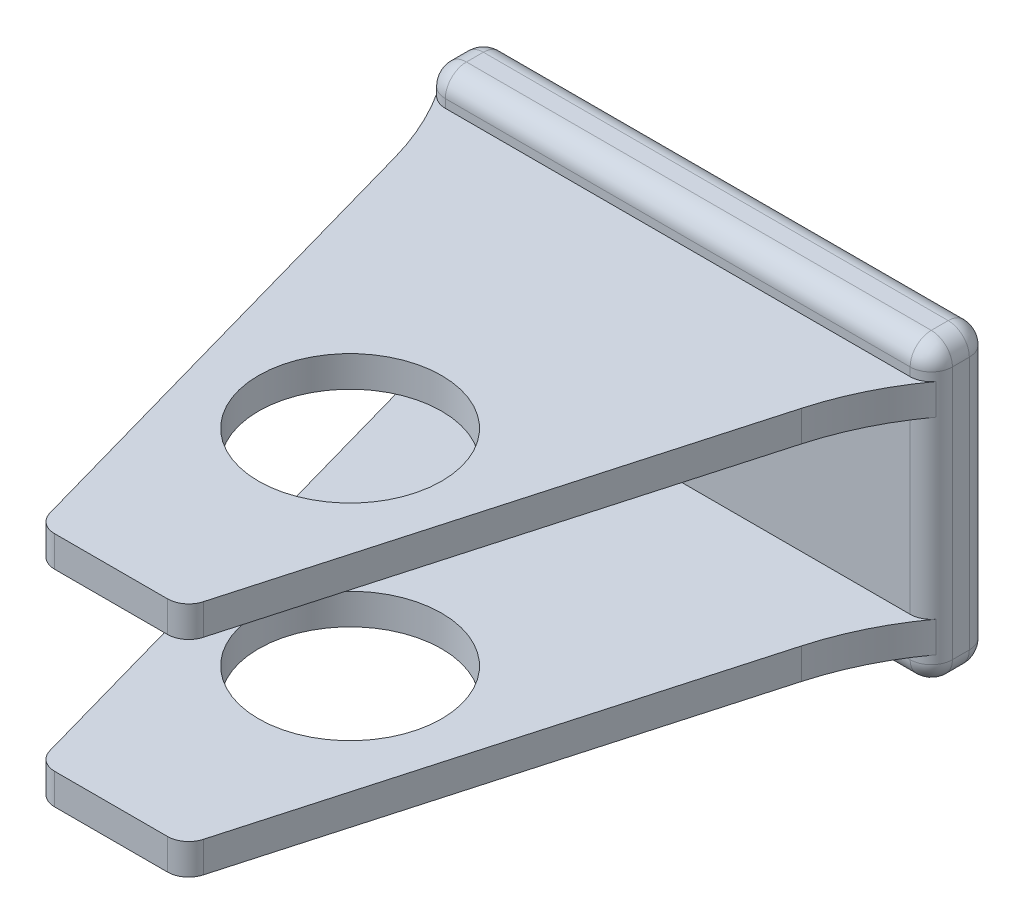
SolidWorks part; units mm, degrees
ref_plane "Front Plane" through (0, 0, 0) normal (0, 0, 1) x (1, 0, 0)
ref_plane "Top Plane" through (0, 0, 0) normal (0, 1, 0) x (1, 0, 0)
ref_plane "Right Plane" through (0, 0, 0) normal (1, 0, 0) x (0, 0, -1)
sketch "Sketch1" plane through (0, 0, 0) normal (0, 0, 1) x (1, 0, 0)
  line L1 (-60, -35) -> (60, -35)
  line L2 (-60, -35) -> (-60, 35)
  line L3 (-60, 35) -> (60, 35)
  line L4 (60, -35) -> (60, 35)
  line L5 (-60, -35) -> (60, 35) construction
  line L6 (-60, 35) -> (60, -35) construction
  circle A0 centre (0, 0) radius 13.3333
  point P0 (0, 0)
  dimension "D1" = 120
  dimension "D2" = 70
extrude "Boss-Extrude1" add sketch "Sketch1" along normal blind 14
ref_plane "Plane1" through (0, -28, 0) normal (0, -1, 0) x (-1, 0, 0)
sketch "Sketch3" plane through (0, -28, 0) normal (0, -1, 0) x (-1, 0, 0)
  line L0 (60, -14) -> (40.2879, -14)
  line L1 (60, -14) -> (-60, -14) construction
  line L2 (53.6392, -20.3738) -> (17.8194, -147.3992)
  line L3 (17.8194, -147.3992) -> (-16.4464, -147.3992)
  line L4 (0.6865, -1048.0766) -> (0.6865, 48951.9234) construction
  line L5 (-52.2662, -20.3738) -> (-16.4464, -147.3992)
  line L6 (-58.627, -14) -> (-38.9149, -14)
  line L7 (-58.627, -14) -> (-60, -14)
  line L8 (40.2879, -14) -> (-38.9149, -14)
  line L9 (-52.2662, -20.3738) -> (-54.0636, -14)
  line L10 (53.6392, -20.3738) -> (55.4365, -14)
  point P12 (0.6865, -147.3992)
extrude "Boss-Extrude2" add sketch "Sketch3" against normal blind 7.3 contours L4 L3 L2 L8 | L3 L4 L8 L5 region at (-20.2977, -28, 69.0647) region at (18.9247, -28, 69.0647)
mirror "Mirror1" about plane through (0, 0, 0) normal (0, 1, 0) of "Boss-Extrude2"
sketch "Sketch4" plane through (0, -28, 0) normal (0, -1, 0) x (1, 0, 0)
  line L0 (-0.6865, -951.9234) -> (-0.6865, 49048.0766) construction
  line L1 (-17.8194, 147.3992) -> (16.4464, 147.3992) construction
  circle A0 centre (-0.6865, 90.853) radius 21.6667
  point P5 (-0.6865, 147.3992)
  dimension "D1" = 43.3333
extrude "Cut-Extrude1" cut sketch "Sketch4" against normal through all
fillet "Fillet1" radius 5 12 edges at (-60, 0, 14) (-60, 0, 0) (0, 35, 14) (-60, 35, 7) (0, 35, 0) (60, 0, 14) (60, 35, 7) (60, 0, 0) (-60, -35, 7) (0, -35, 14) (60, -35, 7) (0, -35, 0)
fillet "Fillet2" radius 5 4 edges at (-17.8194, 24.35, 147.3992) (16.4464, 24.35, 147.3992) (16.4464, -24.35, 147.3992) (-17.8194, -24.35, 147.3992)
scale "Scale1" scale about centroid uniform scaling yes scale factor 0.15
fillet "Fillet3" radius 10 4 edges at (7.8011, -3.6525, 34.1333) (7.8011, 3.6525, 34.1333) (-8.6248, -3.6525, 34.1304) (-8.6248, 3.6525, 34.1304)
